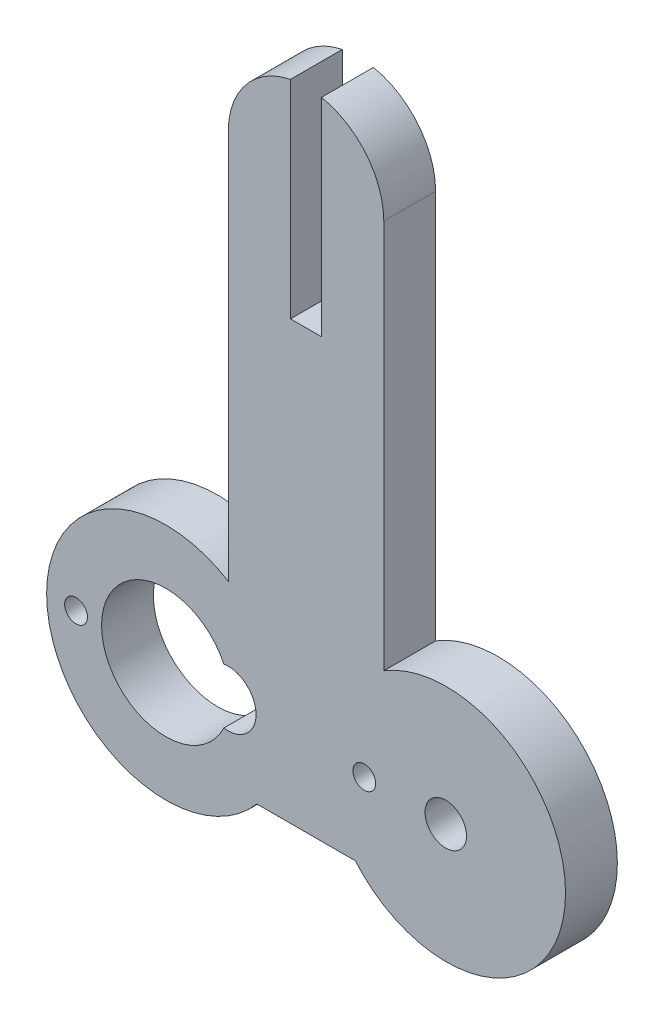
SolidWorks part; units mm, degrees
ref_plane "Front Plane" through (0, 0, 0) normal (0, 0, 1) x (1, 0, 0)
ref_plane "Top Plane" through (0, 0, 0) normal (0, 1, 0) x (1, 0, 0)
ref_plane "Right Plane" through (0, 0, 0) normal (1, 0, 0) x (0, 0, -1)
sketch "Model" plane through (0, 0, 0) normal (0, 0, 1) x (1, 0, 0)
  line L0 (36.0101, 56.158) -> (36.0101, 56.1561)
  line L1 (21.0101, 56.1288) -> (21.0101, 56.1269)
  line L2 (30.0101, 76.0529) -> (27.0101, 76.0529)
  line L3 (30.0101, 76.0529) -> (30.0101, 101.0529)
  line L4 (27.0101, 101.0529) -> (27.0101, 76.0529)
  line L5 (48.6459, 55.6974) -> (48.2061, 56.005)
  line L6 (48.2061, 56.005) -> (47.7295, 56.2862)
  line L7 (3.5394, 47.3443) -> (3.496, 46.7948)
  line L8 (47.2624, 56.5503) -> (46.7615, 56.7857)
  line L9 (3.5555, 45.1556) -> (3.6167, 44.6079)
  line L10 (46.2712, 57.0039) -> (45.7505, 57.1912)
  line L11 (49.918, 54.6592) -> (49.5023, 55.0245)
  line L12 (45.7505, 57.1912) -> (45.2416, 57.3615)
  line L13 (3.6167, 44.6079) -> (3.7197, 44.0724)
  line L14 (46.7615, 56.7857) -> (46.2712, 57.0039)
  line L15 (3.4952, 46.2496) -> (3.5042, 45.6985)
  line L16 (49.5023, 55.0245) -> (49.094, 55.3727)
  line L17 (3.5923, 47.887) -> (3.5394, 47.3443)
  line L18 (47.7295, 56.2862) -> (47.2624, 56.5503)
  line L19 (51.3456, 53.0148) -> (51.0054, 53.4511)
  line L20 (49.094, 55.3727) -> (48.6459, 55.6974)
  line L21 (3.7197, 44.0724) -> (3.8326, 43.5329)
  line L22 (3.6876, 48.4299) -> (3.5923, 47.887)
  line L23 (43.6363, 57.7069) -> (43.1041, 57.7772)
  line L24 (15.4851, 57.8156) -> (14.9342, 57.8314)
  line L25 (50.2912, 54.2734) -> (49.918, 54.6592)
  line L26 (3.496, 46.7948) -> (3.4952, 46.2496)
  line L27 (8.7862, 46.3327) -> (8.8373, 47.1266)
  line L28 (51.0054, 53.4511) -> (50.6708, 53.8709)
  line L29 (44.1827, 57.6201) -> (43.6363, 57.7069)
  line L30 (45.2416, 57.3615) -> (44.7057, 57.4992)
  line L31 (3.5042, 45.6985) -> (3.5555, 45.1556)
  line L32 (42.5519, 57.8124) -> (42.0156, 57.8315)
  line L33 (8.9895, 44.758) -> (8.8373, 45.5388)
  line L34 (8.8373, 47.1266) -> (8.9895, 47.9075)
  line L35 (38.7875, 57.3771) -> (38.2608, 57.2073)
  line L36 (3.8326, 43.5329) -> (3.9863, 43.0098)
  line L37 (13.2989, 57.7017) -> (12.7549, 57.6131)
  line L38 (50.6708, 53.8709) -> (50.2912, 54.2734)
  line L39 (16.5765, 57.7161) -> (16.0295, 57.784)
  line L40 (8.8373, 45.5388) -> (8.7862, 46.3327)
  line L41 (3.7921, 48.965) -> (3.6876, 48.4299)
  line L42 (15.651, 34.8635) -> (16.2011, 34.8971)
  line L43 (40.3776, 57.714) -> (39.8475, 57.6305)
  line L44 (52.1847, 51.6229) -> (51.9362, 52.0986)
  line L45 (44.7057, 57.4992) -> (44.1827, 57.6201)
  line L46 (14.9342, 57.8314) -> (14.3893, 57.8108)
  line L47 (43.1041, 57.7772) -> (42.5519, 57.8124)
  line L48 (42.0156, 57.8315) -> (41.4624, 57.8148)
  line L49 (16.7402, 34.9791) -> (17.2847, 35.0648)
  line L50 (39.3072, 57.5109) -> (38.7875, 57.3771)
  line L51 (14.0108, 34.8742) -> (14.5556, 34.8521)
  line L52 (39.8475, 57.6305) -> (39.3072, 57.5109)
  line L53 (18.1818, 57.3784) -> (17.6534, 57.513)
  line L54 (16.2011, 34.8971) -> (16.7402, 34.9791)
  line L55 (13.4642, 34.9451) -> (14.0108, 34.8742)
  line L56 (17.1153, 57.6326) -> (16.5765, 57.7161)
  line L57 (14.3893, 57.8108) -> (13.8393, 57.7742)
  line L58 (3.9863, 43.0098) -> (4.1499, 42.4834)
  line L59 (16.0295, 57.784) -> (15.4851, 57.8156)
  line L60 (12.7549, 57.6131) -> (12.2239, 57.4892)
  line L61 (13.8393, 57.7742) -> (13.2989, 57.7017)
  line L62 (37.7562, 57.0244) -> (37.2478, 56.8061)
  line L63 (41.4624, 57.8148) -> (40.9267, 57.7824)
  line L64 (51.9362, 52.0986) -> (51.6383, 52.5651)
  line L65 (51.6383, 52.5651) -> (51.3456, 53.0148)
  line L66 (19.7249, 56.8047) -> (19.2191, 57.0238)
  line L67 (15.1065, 34.8334) -> (15.651, 34.8635)
  line L68 (4.1499, 42.4834) -> (4.3529, 41.9773)
  line L69 (12.3866, 35.1417) -> (12.924, 35.0192)
  line L70 (4.2899, 50.5342) -> (4.0937, 50.0191)
  line L71 (12.2239, 57.4892) -> (11.6908, 57.3493)
  line L72 (12.924, 35.0192) -> (13.4642, 34.9451)
  line L73 (17.2847, 35.0648) -> (17.8134, 35.1979)
  line L74 (17.6534, 57.513) -> (17.1153, 57.6326)
  line L75 (40.9267, 57.7824) -> (40.3776, 57.714)
  line L76 (38.2608, 57.2073) -> (37.7562, 57.0244)
  line L77 (21.0101, 56.1269) -> (20.9062, 56.1883)
  line L78 (14.5556, 34.8521) -> (15.1065, 34.8334)
  line L79 (36.0921, 56.2048) -> (36.0101, 56.1561)
  line L80 (11.856, 35.2671) -> (12.3866, 35.1417)
  line L81 (4.0937, 50.0191) -> (3.9385, 49.4965)
  line L82 (4.7385, 51.5339) -> (4.4943, 51.0397)
  line L83 (40.4698, 43.5148) -> (39.9911, 43.8309)
  line L84 (20.9062, 56.1883) -> (20.7658, 56.2687)
  line L85 (8.2689, 55.6581) -> (7.8258, 55.3304)
  line L86 (38.8377, 45.7613) -> (38.7862, 46.3327)
  line L87 (38.8377, 46.9041) -> (38.9903, 47.4571)
  line L88 (4.3529, 41.9773) -> (4.5658, 41.4689)
  line L89 (18.7061, 57.2083) -> (18.1818, 57.3784)
  line L90 (7.4115, 54.9759) -> (7.0014, 54.6076)
  line L91 (17.8134, 35.1979) -> (18.3473, 35.3349)
  line L92 (10.1588, 56.7628) -> (9.6617, 56.5248)
  line L93 (37.2478, 56.8061) -> (36.811, 56.6001)
  line L94 (19.2191, 57.0238) -> (18.7061, 57.2083)
  line L95 (5.9103, 53.3827) -> (5.5772, 52.9436)
  line L96 (11.6908, 57.3493) -> (11.174, 57.1753)
  line L97 (39.2392, 44.6914) -> (38.9903, 45.2083)
  line L98 (22.5433, 48.5385) -> (22.9341, 48.2024)
  line L99 (7.0014, 54.6076) -> (6.6229, 54.2151)
  line L100 (11.174, 57.1753) -> (10.6566, 56.9855)
  line L101 (39.9911, 43.8309) -> (39.5764, 44.2273)
  line L102 (53.2582, 48.5467) -> (53.1546, 49.0745)
  line L103 (38.9903, 47.4571) -> (39.2392, 47.974)
  line L104 (22.9341, 44.463) -> (22.5433, 44.1269)
  line L105 (5.5772, 52.9436) -> (5.2803, 52.4862)
  line L106 (20.7658, 56.2687) -> (20.1793, 56.5918)
  line L107 (45.1733, 46.6196) -> (45.1733, 46.0459)
  line L108 (36.2198, 56.2778) -> (36.0921, 56.2048)
  line L109 (39.2392, 47.974) -> (39.5764, 48.4381)
  line L110 (43.7491, 43.6621) -> (43.2439, 43.3902)
  line L111 (9.6617, 56.5248) -> (9.1875, 56.2555)
  line L112 (52.4375, 51.1307) -> (52.1847, 51.6229)
  line L113 (21.0968, 43.635) -> (20.5821, 43.6631)
  line L114 (3.9385, 49.4965) -> (3.7921, 48.965)
  line L115 (23.6862, 46.3327) -> (23.637, 45.8196)
  line L116 (23.4912, 45.3251) -> (23.254, 44.8674)
  line L117 (22.0956, 43.8712) -> (21.6075, 43.7052)
  line L118 (36.811, 56.6001) -> (36.2198, 56.2778)
  line L119 (18.861, 35.5179) -> (19.3794, 35.705)
  line L120 (38.9903, 45.2083) -> (38.8377, 45.7613)
  line L121 (38.7862, 46.3327) -> (38.8377, 46.9041)
  line L122 (10.8164, 35.6155) -> (11.3326, 35.44)
  line L123 (6.015, 39.1535) -> (6.3622, 38.7254)
  line L124 (40.9974, 43.2893) -> (40.4698, 43.5148)
  line L125 (5.3719, 40.0404) -> (5.6769, 39.5813)
  line L126 (9.5862, 49.3789) -> (10.0207, 50.0453)
  line L127 (8.7152, 55.9714) -> (8.2689, 55.6581)
  line L128 (4.5658, 41.4689) -> (4.8162, 40.9845)
  line L129 (5.2803, 52.4862) -> (4.9903, 52.0175)
  line L130 (39.5764, 48.4381) -> (39.9911, 48.8346)
  line L131 (4.4943, 51.0397) -> (4.2899, 50.5342)
  line L132 (20.5821, 49.0023) -> (21.0968, 49.0305)
  line L133 (22.9341, 48.2024) -> (23.254, 47.7981)
  line L134 (14.8005, 40.1355) -> (14.0085, 40.2103)
  line L135 (9.2406, 44.0031) -> (8.9895, 44.758)
  line L136 (23.4912, 47.3404) -> (23.637, 46.8459)
  line L137 (40.9974, 49.3761) -> (41.5567, 49.5038)
  line L138 (22.6082, 37.7385) -> (23.0206, 38.1048)
  line L139 (10.6566, 56.9855) -> (10.1588, 56.7628)
  line L140 (35.9594, 94.5844) -> (35.808, 95.4433)
  line L141 (18.3473, 35.3349) -> (18.861, 35.5179)
  line L142 (19.7205, 50.3361) -> (20.1942, 49.6969)
  line L143 (44.0033, 35.011) -> (45.0682, 35.2534)
  line L144 (40.4698, 49.1506) -> (40.9974, 49.3761)
  line L145 (7.961, 37.2282) -> (8.4064, 36.9137)
  line L146 (14.0085, 40.2103) -> (13.2325, 40.3859)
  line L147 (38.6021, 35.3419) -> (39.6599, 35.0705)
  line L148 (21.3148, 36.7307) -> (21.7554, 37.0516)
  line L149 (44.1976, 44.0198) -> (43.7491, 43.6621)
  line L150 (8.86, 36.6005) -> (9.3334, 36.33)
  line L151 (19.8731, 35.9362) -> (20.3716, 36.1716)
  line L152 (21.0968, 49.0305) -> (21.6075, 48.9603)
  line L153 (35.5578, 96.2788) -> (35.2124, 97.0797)
  line L154 (14.8005, 52.5299) -> (15.5956, 52.5027)
  line L155 (44.5751, 44.4518) -> (44.1976, 44.0198)
  line L156 (7.1259, 37.9387) -> (7.5391, 37.583)
  line L157 (22.0956, 48.7943) -> (22.5433, 48.5385)
  line L158 (19.1689, 50.9093) -> (19.7205, 50.3361)
  line L159 (41.8288, 34.8338) -> (42.9202, 34.8707)
  line L160 (52.6392, 50.6335) -> (52.4375, 51.1307)
  line L161 (53.3632, 48.0103) -> (53.2582, 48.5467)
  line L162 (17.8693, 40.8438) -> (17.1427, 40.5199)
  line L163 (23.637, 46.8459) -> (23.6862, 46.3327)
  line L164 (22.2005, 37.3771) -> (22.6082, 37.7385)
  line L165 (41.5567, 49.5038) -> (42.1298, 49.5295)
  line L166 (23.254, 47.7981) -> (23.4912, 47.3404)
  line L167 (43.7491, 49.0034) -> (44.1976, 48.6457)
  line L168 (45.0709, 45.4814) -> (44.8693, 44.9443)
  line L169 (42.6983, 43.213) -> (42.1298, 43.1359)
  line L170 (23.0206, 38.1048) -> (23.2683, 38.3708)
  line L171 (16.3806, 52.3739) -> (17.1427, 52.1456)
  line L172 (44.8693, 47.7212) -> (45.0709, 47.184)
  line L173 (10.537, 50.6506) -> (11.1265, 51.1848)
  line L174 (42.1298, 49.5295) -> (42.6983, 49.4525)
  line L175 (11.7796, 41.0264) -> (11.1265, 41.4806)
  line L176 (12.4855, 52.006) -> (13.2325, 52.2795)
  line L177 (20.3716, 36.1716) -> (20.8409, 36.4491)
  line L178 (9.2406, 48.6624) -> (9.5862, 49.3789)
  line L179 (16.3806, 40.2916) -> (15.5956, 40.1627)
  line L180 (20.1942, 49.6969) -> (20.5821, 49.0023)
  line L181 (53.5151, 47.1396) -> (53.3632, 48.0103)
  line L182 (4.9903, 52.0175) -> (4.7385, 51.5339)
  line L183 (20.8409, 36.4491) -> (21.3148, 36.7307)
  line L184 (39.5764, 44.2273) -> (39.2392, 44.6914)
  line L185 (53.1546, 49.0745) -> (52.9981, 49.6053)
  line L186 (36.0101, 56.158) -> (36.0101, 93.7137)
  line L187 (12.4855, 40.6594) -> (11.7796, 41.0264)
  line L188 (49.094, 55.3727) -> (48.6459, 55.6974)
  line L189 (6.6229, 54.2151) -> (6.2496, 53.8096)
  line L190 (48.6459, 55.6974) -> (48.2061, 56.005)
  line L191 (6.7396, 38.3319) -> (7.1259, 37.9387)
  line L192 (47.7295, 56.2862) -> (47.2624, 56.5503)
  line L193 (5.6769, 39.5813) -> (6.015, 39.1535)
  line L194 (11.1265, 41.4806) -> (10.537, 42.0148)
  line L195 (49.918, 54.6592) -> (49.5023, 55.0245)
  line L196 (13.2325, 40.3859) -> (12.4855, 40.6594)
  line L197 (45.1733, 46.0459) -> (45.0709, 45.4814)
  line L198 (23.637, 45.8196) -> (23.4912, 45.3251)
  line L199 (7.5391, 37.583) -> (7.961, 37.2282)
  line L200 (42.1298, 43.1359) -> (41.5567, 43.1617)
  line L201 (10.0207, 50.0453) -> (10.537, 50.6506)
  line L202 (5.0763, 40.4986) -> (5.3719, 40.0404)
  line L203 (10.3117, 35.8373) -> (10.8164, 35.6155)
  line L204 (23.254, 44.8674) -> (22.9341, 44.463)
  line L205 (19.3794, 35.705) -> (19.8731, 35.9362)
  line L206 (6.2496, 53.8096) -> (5.9103, 53.3827)
  line L207 (45.0709, 47.184) -> (45.1733, 46.6196)
  line L208 (21.6075, 43.7052) -> (21.0968, 43.635)
  line L209 (21.7554, 37.0516) -> (22.2005, 37.3771)
  line L210 (9.3334, 36.33) -> (9.8147, 36.0613)
  line L211 (9.1875, 56.2555) -> (8.7152, 55.9714)
  line L212 (39.9911, 48.8346) -> (40.4698, 49.1506)
  line L213 (7.8258, 55.3304) -> (7.4115, 54.9759)
  line L214 (8.4064, 36.9137) -> (8.86, 36.6005)
  line L215 (4.8162, 40.9845) -> (5.0763, 40.4986)
  line L216 (6.3622, 38.7254) -> (6.7396, 38.3319)
  line L217 (36.0101, 93.7137) -> (35.9594, 94.5844)
  line L218 (10.0207, 42.6201) -> (9.5862, 43.2865)
  line L219 (9.5862, 43.2865) -> (9.2406, 44.0031)
  line L220 (10.537, 42.0148) -> (10.0207, 42.6201)
  line L221 (9.8147, 36.0613) -> (10.3117, 35.8373)
  line L222 (52.9981, 49.6053) -> (52.8448, 50.1196)
  line L223 (35.808, 95.4433) -> (35.5578, 96.2788)
  line L224 (17.1427, 52.1456) -> (17.8693, 51.8216)
  line L225 (44.5751, 48.2136) -> (44.8693, 47.7212)
  line L226 (37.5748, 35.7125) -> (38.6021, 35.3419)
  line L227 (18.5484, 41.2582) -> (17.8693, 40.8438)
  line L228 (52.7911, 42.3951) -> (53.1159, 43.4378)
  line L229 (11.7796, 51.6391) -> (12.4855, 52.006)
  line L230 (34.2555, 98.5346) -> (33.6569, 99.169)
  line L231 (15.5956, 52.5027) -> (16.3806, 52.3739)
  line L232 (31.4807, 100.6003) -> (30.6612, 100.8986)
  line L233 (46.1052, 35.5957) -> (47.1052, 36.0348)
  line L234 (53.1159, 43.4378) -> (53.3403, 44.5066)
  line L235 (22.244, 97.835) -> (21.8079, 97.0797)
  line L236 (50.5597, 38.6682) -> (51.2481, 39.516)
  line L237 (48.9579, 37.1869) -> (49.794, 37.8895)
  line L238 (21.2123, 95.4433) -> (21.0608, 94.5844)
  line L239 (21.8079, 97.0797) -> (21.4624, 96.2788)
  line L240 (21.0608, 94.5844) -> (21.0101, 93.7137)
  line L241 (22.7648, 98.5346) -> (22.244, 97.835)
  line L242 (43.2439, 49.2752) -> (43.7491, 49.0034)
  line L243 (24.7601, 100.2089) -> (24.0314, 99.7296)
  line L244 (19.1689, 41.7561) -> (18.5484, 41.2582)
  line L245 (24.0314, 99.7296) -> (23.3633, 99.169)
  line L246 (49.794, 37.8895) -> (50.5597, 38.6682)
  line L247 (26.3591, 100.8986) -> (25.5395, 100.6003)
  line L248 (32.2601, 100.2089) -> (31.4807, 100.6003)
  line L249 (33.9502, 38.1065) -> (34.7667, 37.3813)
  line L250 (52.3688, 41.3879) -> (52.7911, 42.3951)
  line L251 (35.6484, 36.7368) -> (36.5872, 36.1789)
  line L252 (53.3403, 44.5066) -> (53.5036, 45.3752)
  line L253 (34.7667, 37.3813) -> (35.6484, 36.7368)
  line L254 (36.5872, 36.1789) -> (37.5748, 35.7125)
  line L255 (33.2061, 38.9058) -> (33.9502, 38.1065)
  line L256 (51.853, 40.4253) -> (52.3688, 41.3879)
  line L257 (36.0101, 56.158) -> (36.0101, 93.7137)
  line L258 (23.3633, 99.169) -> (22.7648, 98.5346)
  line L259 (21.0101, 93.7137) -> (21.0101, 56.1288)
  line L260 (27.0101, 101.0529) -> (26.3591, 100.8986)
  line L261 (23.7664, 38.9058) -> (33.2061, 38.9058)
  line L262 (53.5621, 46.2571) -> (53.5151, 47.1396)
  line L263 (47.2624, 56.5503) -> (46.7615, 56.7857)
  line L264 (50.2912, 54.2734) -> (49.918, 54.6592)
  line L265 (45.7505, 57.1912) -> (45.2416, 57.3615)
  line L266 (48.2061, 56.005) -> (47.7295, 56.2862)
  line L267 (46.7615, 56.7857) -> (46.2712, 57.0039)
  line L268 (46.2712, 57.0039) -> (45.7505, 57.1912)
  line L269 (49.5023, 55.0245) -> (49.094, 55.3727)
  line L270 (33.6569, 99.169) -> (32.9888, 99.7296)
  line L271 (23.2683, 38.3708) -> (23.7664, 38.9058)
  line L272 (25.5395, 100.6003) -> (24.7601, 100.2089)
  line L273 (32.9888, 99.7296) -> (32.2601, 100.2089)
  line L274 (47.1052, 36.0348) -> (48.0589, 36.5668)
  line L275 (20.1942, 42.9686) -> (19.7205, 42.3294)
  line L276 (34.7763, 97.835) -> (34.2555, 98.5346)
  line L277 (51.2481, 39.516) -> (51.853, 40.4253)
  line L278 (53.5036, 45.3752) -> (53.5621, 46.2571)
  line L279 (45.0682, 35.2534) -> (46.1052, 35.5957)
  line L280 (14.0085, 52.4551) -> (14.8005, 52.5299)
  line L281 (35.2124, 97.0797) -> (34.7763, 97.835)
  line L282 (42.6983, 49.4525) -> (43.2439, 49.2752)
  line L283 (48.0589, 36.5668) -> (48.9579, 37.1869)
  line L284 (15.5956, 40.1627) -> (14.8005, 40.1355)
  line L285 (30.6612, 100.8986) -> (30.0101, 101.0529)
  line L286 (42.9202, 34.8707) -> (44.0033, 35.011)
  line L287 (44.1976, 48.6457) -> (44.5751, 48.2136)
  line L288 (21.4624, 96.2788) -> (21.2123, 95.4433)
  line L289 (40.7387, 34.9006) -> (41.8288, 34.8338)
  line L290 (17.8693, 51.8216) -> (18.5484, 51.4072)
  line L291 (17.1427, 40.5199) -> (16.3806, 40.2916)
  line L292 (18.5484, 51.4072) -> (19.1689, 50.9093)
  line L293 (13.2325, 52.2795) -> (14.0085, 52.4551)
  line L294 (39.6599, 35.0705) -> (40.7387, 34.9006)
  line L295 (19.7205, 42.3294) -> (19.1689, 41.7561)
  line L296 (11.1265, 51.1848) -> (11.7796, 51.6391)
  line L297 (44.8693, 44.9443) -> (44.5751, 44.4518)
  line L298 (20.5821, 43.6631) -> (20.1942, 42.9686)
  line L299 (52.8448, 50.1196) -> (52.6392, 50.6335)
  line L300 (11.3326, 35.44) -> (11.856, 35.2671)
  line L301 (21.6075, 48.9603) -> (22.0956, 48.7943)
  line L302 (8.9895, 47.9075) -> (9.2406, 48.6624)
  line L303 (20.1793, 56.5918) -> (19.7249, 56.8047)
  line L304 (41.5567, 43.1617) -> (40.9974, 43.2893)
  line L305 (43.2439, 43.3902) -> (42.6983, 43.213)
  line L306 (22.5433, 44.1269) -> (22.0956, 43.8712)
  circle A0 centre (6.3262, 46.3327) radius 1.1
  circle A1 centre (34.1262, 46.3327) radius 1.1
sketch "Sketch2" plane through (0, 0, 0) normal (0, 0, 1) x (1, 0, 0)
  circle A0 centre (41.9862, 46.3327) radius 3.2
sketch "Sketch3" plane through (0, 0, 0) normal (0, 0, 1) x (1, 0, 0)
  line L0 (23.7664, 38.9058) -> (33.2061, 38.9058)
  line L1 (27.0101, 81.0529) -> (27.0101, 101.0529)
  line L3 (30.0101, 81.0529) -> (30.0101, 101.0529)
  line L4 (36.0101, 93.7137) -> (36.0101, 56.158)
  line L5 (21.0101, 56.1288) -> (21.0101, 93.7137)
  line L6 (30.0101, 101.0529) -> (30.0101, 101.0622)
  line L7 (27.0101, 101.0529) -> (27.0101, 101.0622)
  line L8 (33.2061, 38.9058) -> (33.2647, 38.9058)
  line L9 (21.0101, 56.1288) -> (21.0101, 56.1278)
  line L10 (21.0101, 56.1278) -> (21.0101, 56.1268)
  line L11 (36.0101, 56.158) -> (36.0101, 56.1531)
  line L13 (27.0101, 81.0529) -> (30.0101, 81.0529)
  arc A1 (20.5821, 49.0023) -> (20.5821, 43.6631) centre (14.9862, 46.3327) ccw
  arc A2 (20.5821, 43.6631) -> (20.5821, 49.0023) centre (20.9862, 46.3327) ccw
  arc A3 (21.0101, 56.1278) -> (23.7664, 38.9058) centre (14.9864, 46.3322) ccw
  arc A4 (33.2647, 38.9058) -> (36.0101, 56.1549) centre (42.0359, 46.3528) ccw
  arc A5 (36.0101, 93.7137) -> (30.0101, 101.0622) centre (28.5101, 93.7137) ccw
  arc A6 (27.0101, 101.0622) -> (21.0101, 93.7137) centre (28.5101, 93.7137) ccw
  circle A7 centre (6.3262, 46.3327) radius 1.1
  circle A8 centre (34.1262, 46.3327) radius 1.1
  point P0 (41.9862, 46.3327)
  dimension "D2" = 11.5062
  dimension "D4" = 6.2
  dimension "D5" = 2.7
  dimension "D6" = 2.2
  dimension "D7" = 2.2
  dimension "D3" = 27
  dimension "D8" = 7.86
  dimension "D9" = 6
  dimension "D10" = 8.66
extrude "Boss-Extrude1" add sketch "Sketch3" along normal blind 5 contours L7 A6 L5 L9 A3 L0 L8 A4 L11 L4 A5 L6 L3 L1 A8 A7 A2 A1 region at (29.7812, 59.3142, 0)
sketch "Sketch5" plane through (0, 0, 5) normal (0, 0, 1) x (1, 0, 0)
  circle A0 centre (41.9862, 46.3327) radius 2
extrude "Cut-Extrude1" cut sketch "Sketch5" against normal blind 10 contours A0
